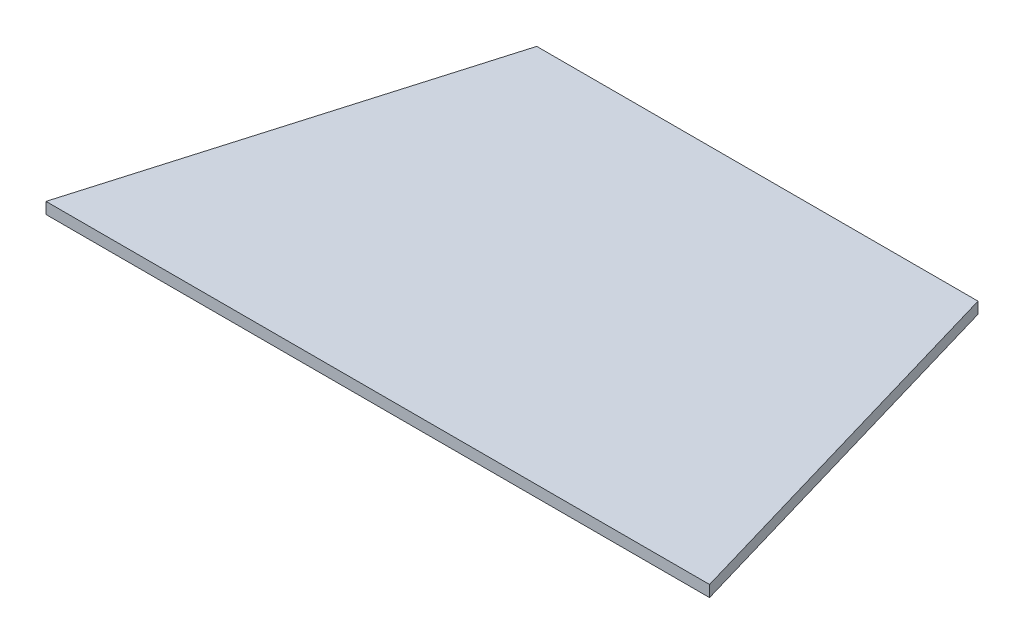
SolidWorks part; units mm, degrees
ref_plane "Front Plane" through (0, 0, 0) normal (0, 0, 1) x (1, 0, 0)
ref_plane "Top Plane" through (0, 0, 0) normal (0, 1, 0) x (1, 0, 0)
ref_plane "Right Plane" through (0, 0, 0) normal (1, 0, 0) x (0, 0, -1)
sketch "Sketch1" plane through (0, 0, 0) normal (0, 1, 0) x (1, 0, 0)
  line L0 (5.2, 0) -> (180, 0)
  line L3 (90, 0) -> (90, 100) construction
  line L5 (5.2, 0) -> (34.4799, 100)
  line L6 (180, 0) -> (150.7201, 100)
  line L7 (34.4799, 100) -> (150.7201, 100)
extrude "Boss-Extrude1" add sketch "Sketch1" along normal blind 3
